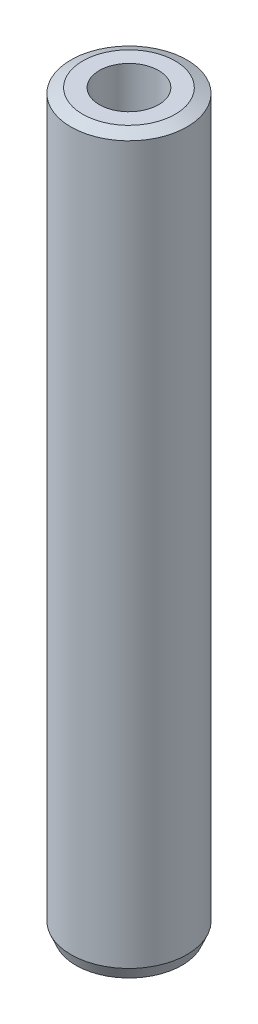
SolidWorks part; units mm, degrees
ref_plane "Front Plane" through (0, 0, 0) normal (0, 0, 1) x (1, 0, 0)
ref_plane "Top Plane" through (0, 0, 0) normal (0, 1, 0) x (1, 0, 0)
ref_plane "Right Plane" through (0, 0, 0) normal (1, 0, 0) x (0, 0, -1)
sketch "Sketch1" plane through (0, 0, 0) normal (0, 1, 0) x (1, 0, 0)
  circle A0 centre (0, 0) radius 47.5
  dimension "SHAFT_OD" = 95
extrude "Boss-Extrude1" add sketch "Sketch1" along normal blind 600
sketch "Sketch2" plane through (0, 0, 0) normal (0, 1, 0) x (1, 0, 0)
  circle A0 centre (0, 0) radius 24.2454
  dimension "BORE_D" = 48.4908
extrude "Cut-Extrude1" cut sketch "Sketch2" along normal through all
chamfer "Chamfer1" distance 4.1322 angle 66.899 2 edges at (0, 600, 47.5) (0, 0, 47.5) first distance on face at (0, 600, 47.5) first distance on face at (0, 0, 24.2454)
